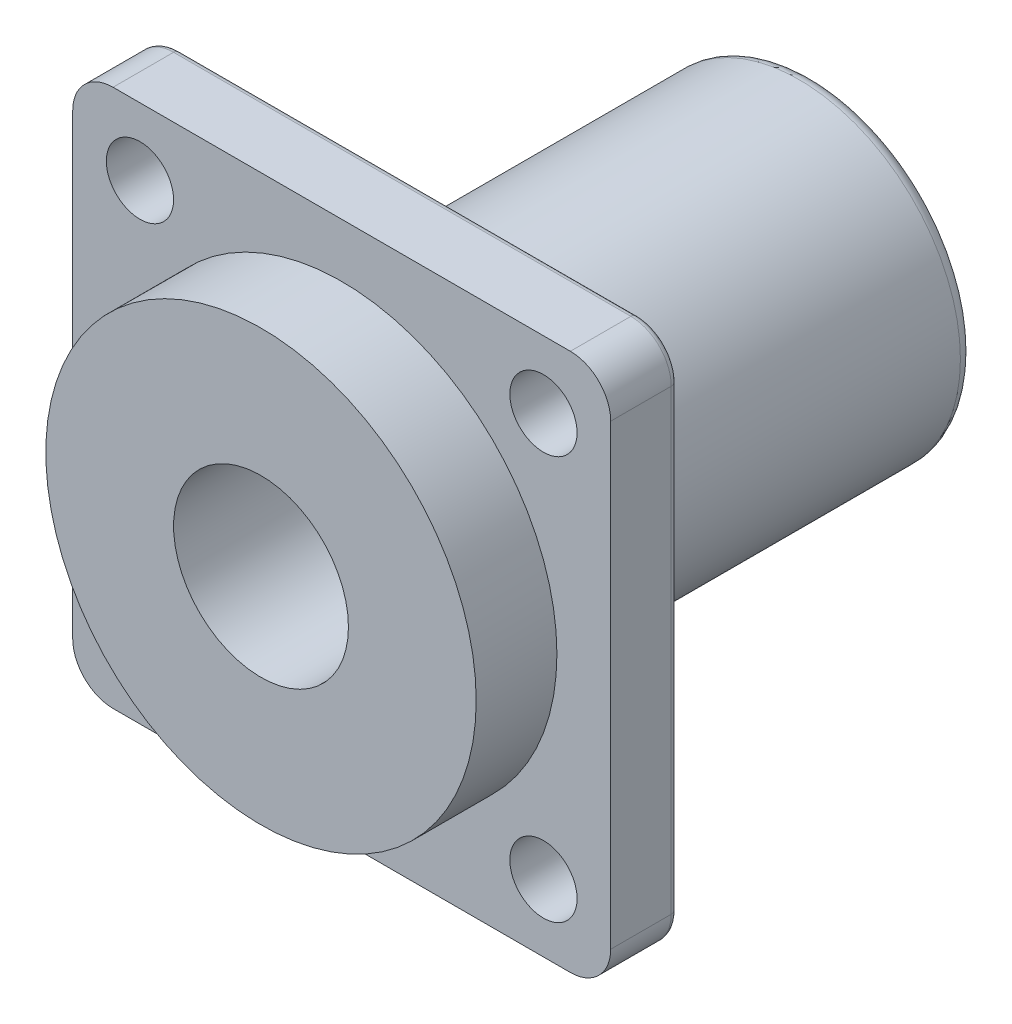
SolidWorks part; units mm, degrees
ref_plane "Front Plane" through (0, 0, 0) normal (0, 0, 1) x (1, 0, 0)
ref_plane "Top Plane" through (0, 0, 0) normal (0, 1, 0) x (1, 0, 0)
ref_plane "Right Plane" through (0, 0, 0) normal (1, 0, 0) x (0, 0, -1)
sketch "Sketch2" plane through (0, 0, 0) normal (0, 0, 1) x (1, 0, 0)
  line L1 (-20, 20) -> (20, 20)
  line L2 (-20, 20) -> (-20, -20)
  line L3 (-20, -20) -> (20, -20)
  line L4 (20, 20) -> (20, -20)
  line L5 (-20, 20) -> (20, -20) construction
  line L6 (-20, -20) -> (20, 20) construction
  line L7 (-15, 15) -> (15, 15) construction
  line L8 (-15, 15) -> (-15, -15) construction
  line L9 (-15, -15) -> (15, -15) construction
  line L10 (15, 15) -> (15, -15) construction
  line L11 (-15, 15) -> (15, -15) construction
  line L12 (-15, -15) -> (15, 15) construction
  circle A0 centre (0, 0) radius 16
  circle A1 centre (0, 0) radius 6.5
  circle A2 centre (-15, 15) radius 2.5
  circle A3 centre (15, 15) radius 2.5
  circle A4 centre (15, -15) radius 2.5
  circle A5 centre (-15, -15) radius 2.5
  circle A6 centre (0, 0) radius 12
  point P0 (0, 0)
  dimension "D4" = 5
  dimension "D5" = 32
  dimension "D6" = 13
  dimension "D7" = 24
  dimension "D1" = 40
  dimension "D2" = 30
  dimension "D3" = 40
extrude "Boss-Extrude5" add sketch "Sketch2" along normal mid plane 5 contours L4 L1 L2 L3 A5 A4 A3 A2 A0 | A0 A1 | A6 A1 region at (0, 19.4343, 0) region at (-15.5475, 0, 0) region at (-11.6606, 0, 0)
extrude "Boss-Extrude8" add sketch "Sketch2<9>" along normal blind 6 from surface contours A0 A1 | A6 A1 region at (-15.5475, 0, 0) region at (-11.6606, 0, 0) starting at face at (-12.5, -15, 2.5)
sketch "Sketch2<9>" plane through (0, 0, 0) normal (0, 0, 1) x (1, 0, 0) same geometry as "Sketch2"
extrude "Boss-Extrude10" add sketch "Sketch2<12>" against normal blind 30 from surface contours A6 A1 region at (-11.6606, 0, 0) starting at face at (-12.5, -15, -2.5)
sketch "Sketch2<12>" plane through (0, 0, 0) normal (0, 0, 1) x (1, 0, 0) same geometry as "Sketch2"
fillet "Fillet1" radius 3 4 edges at (20, 20, 0) (20, -20, 0) (-20, -20, 0) (-20, 20, 0)
fillet "Fillet2" radius 0.5 8 edges at (-19.1213, 19.1213, -2.5) (0, 20, -2.5) (19.1213, 19.1213, -2.5) (20, 0, -2.5) (19.1213, -19.1213, -2.5) (0, -20, -2.5) (-19.1213, -19.1213, -2.5) (-20, 0, -2.5)
fillet "Fillet3" radius 5 1 edges at (12, 0, -2.5)
fillet "Fillet4" radius 1 1 edges at (12, 0, -32.5)
